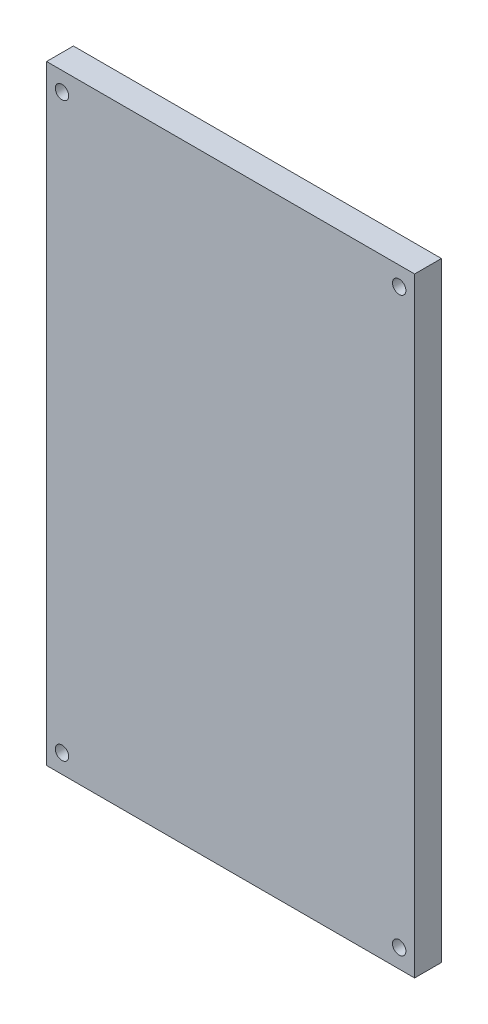
SolidWorks part; units mm, degrees
ref_plane "Front" through (0, 0, 0) normal (0, 0, 1) x (1, 0, 0)
ref_plane "Top" through (0, 0, 0) normal (0, 1, 0) x (1, 0, 0)
ref_plane "Right" through (0, 0, 0) normal (1, 0, 0) x (0, 0, -1)
sketch "arduinoOutline" plane through (0, 0, 0) normal (0, 0, 1) x (1, 0, 0)
  line L0 (0, 32.73) -> (2.54, 35.27) construction
  line L2 (0, 0) -> (0, 32.73) construction
  line L5 (2.54, 35.27) -> (2.54, 36.81) construction
  line L6 (3.54, 37.81) -> (67.6, 37.81) construction
  line L7 (68.6, 36.81) -> (68.6, -14.59) construction
  line L8 (67.6, -15.59) -> (4.06, -15.59) construction
  line L9 (4.06, -15.59) -> (2.54, -14.07) construction
  line L10 (2.54, -14.07) -> (2.54, -2.54) construction
  line L11 (2.54, -2.54) -> (0, 0) construction
  arc A0 (2.54, 36.81) -> (3.54, 37.81) centre (3.54, 36.81) cw construction
  arc A1 (68.6, -14.59) -> (67.6, -15.59) centre (67.6, -14.59) cw construction
  arc A2 (67.6, 37.81) -> (68.6, 36.81) centre (67.6, 36.81) cw construction
  point P8 (2.54, 37.81)
  point P13 (68.6, -15.59)
  point P16 (68.6, 37.81)
  dimension "D6" = 1
  dimension "D9" = 1
  dimension "D10" = 1
  dimension "D1" = 32.73
  dimension "D2" = 135
  dimension "D3" = 3.5921
  dimension "D4" = 2.54
  dimension "D5" = 66.06
  dimension "D7" = 53.4
  dimension "D8" = 64.54
  dimension "D11" = 135
  dimension "D12" = 2.1496
  dimension "D13" = 11.53
  dimension "D14" = 135
  dimension "D15" = 3.5921
sketch "arduinoMountingHolesSketch" plane through (0, 0, 0) normal (0, 0, 1) x (1, 0, 0)
  line L0 (0, 0) -> (0, 32.73) construction
  line L1 (67.6, -15.59) -> (4.06, -15.59) construction
  line L2 (3.54, 37.81) -> (67.6, 37.81) construction
  line L3 (68.6, 36.81) -> (68.6, -14.59) construction
  circle A0 centre (2.54, 2.28) radius 1.25
  circle A1 centre (2.54, 30.45) radius 1.25
  circle A2 centre (54.6, 35.27) radius 1.25
  circle A3 centre (53.35, -13.05) radius 1.25
  dimension "D9" = 2.5
  dimension "D1" = 2.54
  dimension "D2" = 17.87
  dimension "D3" = 2.54
  dimension "D4" = 7.36
  dimension "D5" = 2.54
  dimension "D6" = 14
  dimension "D7" = 2.54
  dimension "D8" = 15.25
sketch "9VbatteryMountingHolesSketch" plane through (0, 0, 0) normal (0, 0, 1) x (1, 0, 0)
  line L0 (0, 16.365) -> (68.6, 16.365) construction
  line L1 (4.875, 40.31) -> (63.725, 40.31) construction
  line L2 (4.875, 40.31) -> (4.875, 88.56) construction
  line L3 (4.875, 88.56) -> (63.725, 88.56) construction
  line L4 (63.725, 40.31) -> (63.725, 88.56) construction
  line L5 (0, 0) -> (0, 32.73) construction
  line L6 (68.6, 36.81) -> (68.6, -14.59) construction
  line L7 (34.3, 40.31) -> (34.3, 88.56) construction
  line L8 (4.875, 64.435) -> (63.725, 64.435) construction
  line L10 (3.54, 37.81) -> (67.6, 37.81) construction
  circle A0 centre (8.625, 86.06) radius 1.25
  circle A1 centre (59.975, 86.06) radius 1.25
  circle A2 centre (8.625, 42.81) radius 1.25
  circle A3 centre (59.975, 42.81) radius 1.25
  point P4 (34.3, 16.365)
  point P5 (34.3, 88.56)
  dimension "D3" = 2.5
  dimension "D1" = 48.25
  dimension "D2" = 58.85
  dimension "D4" = 2.5
  dimension "D5" = 3.75
  dimension "D6" = 2.5
sketch "legBracketMountingHolesSketch" plane through (0, 0, 0) normal (0, 0, 1) x (1, 0, 0)
  line L0 (34.3, 91.06) -> (34.3, 98.06) construction
  line L1 (24.1051, 98.06) -> (44.4949, 98.06) construction
  line L2 (24.1051, 98.06) -> (24.1051, 91.06) construction
  line L3 (24.1051, 91.06) -> (44.4949, 91.06) construction
  line L4 (44.4949, 98.06) -> (44.4949, 91.06) construction
  circle A0 centre (29.2026, 94.56) radius 2
  circle A1 centre (39.3974, 94.56) radius 2
  point P4 (24.1051, 94.56)
  point P5 (34.3, 98.06)
  dimension "D4" = 4
  dimension "D1" = 7
  dimension "D2" = 20.3898
  dimension "D3" = 2.5
  dimension "D5" = 5.0974
sketch "backsideMountingHolesSketch" plane through (0, 0, 0) normal (0, 0, 1) x (1, 0, 0)
  line L0 (0, 41.235) -> (68.6, 41.235) construction
  line L9 (0, 0) -> (0, 32.73) construction
  line L10 (34.3, 40.31) -> (34.3, 88.56) construction
  line L11 (68.6, 36.81) -> (68.6, -14.59) construction
  line L12 (24.1051, 98.06) -> (44.4949, 98.06) construction
  line L13 (4.875, 88.56) -> (63.725, 88.56) construction
  line L14 (4.875, 40.31) -> (4.875, 88.56) construction
  circle A1 centre (2.875, 94.56) radius 1.25
  circle A5 centre (65.725, 94.56) radius 1.25
  circle A6 centre (65.725, -12.09) radius 1.25
  circle A7 centre (2.875, -12.09) radius 1.25
  dimension "D1" = 2.5
  dimension "D2" = 56.825
  dimension "D3" = 6
  dimension "D4" = 2
sketch "Sketch1" plane through (0, 0, 0) normal (0, 0, 1) x (1, 0, 0)
  line L0 (67.6, -15.59) -> (4.06, -15.59) construction
  line L1 (0, 98.06) -> (68.6, 98.06)
  line L2 (0, 98.06) -> (0, -15.59)
  line L3 (0, -15.59) -> (68.6, -15.59)
  line L4 (68.6, 98.06) -> (68.6, -15.59)
  line L5 (0, 0) -> (0, 32.73) construction
  line L6 (68.6, 36.81) -> (68.6, -14.59) construction
  line L9 (24.1051, 98.06) -> (44.4949, 98.06) construction
extrude "bracketBase" add sketch "Sketch1" along normal blind 5
extrude "arduinoMountingHoles" cut sketch "arduinoMountingHolesSketch" against normal through all and the other way blind 22
extrude "9VbatteryMountingHoles" cut sketch "9VbatteryMountingHolesSketch" along normal blind 20
extrude "legBracketMountingHoles" cut sketch "legBracketMountingHolesSketch" along normal blind 13
extrude "backsideMountingHoles" cut sketch "backsideMountingHolesSketch" along normal blind 24
sketch "Sketch2" plane through (0, 0, 5) normal (0, 0, 1) x (1, 0, 0)
  circle A0 centre (53.35, -13.05) radius 1.25 construction
  circle A1 centre (2.54, 2.28) radius 1.25 construction
  circle A2 centre (2.54, 30.45) radius 1.25 construction
  circle A3 centre (54.6, 35.27) radius 1.25 construction
  circle A4 centre (59.975, 42.81) radius 1.25 construction
  circle A5 centre (8.625, 42.81) radius 1.25 construction
  circle A6 centre (59.975, 86.06) radius 1.25 construction
  circle A7 centre (39.3974, 94.56) radius 2 construction
  circle A8 centre (29.2026, 94.56) radius 2 construction
  circle A9 centre (8.625, 86.06) radius 1.25 construction
  circle A10 centre (53.35, -13.05) radius 1.25
  circle A11 centre (2.54, 2.28) radius 1.25
  circle A12 centre (2.54, 30.45) radius 1.25
  circle A13 centre (54.6, 35.27) radius 1.25
  circle A14 centre (59.975, 42.81) radius 1.25
  circle A15 centre (8.625, 42.81) radius 1.25
  circle A16 centre (59.975, 86.06) radius 1.25
  circle A17 centre (39.3974, 94.56) radius 2
  circle A18 centre (29.2026, 94.56) radius 2
  circle A19 centre (8.625, 86.06) radius 1.25
extrude "cover" add sketch "Sketch2" against normal up to surface (5 mm away) up to face at (1.625, -12.09, 0)
equation "\"D2@backsideMountingHolesSketch\"=113.65mm/2"
